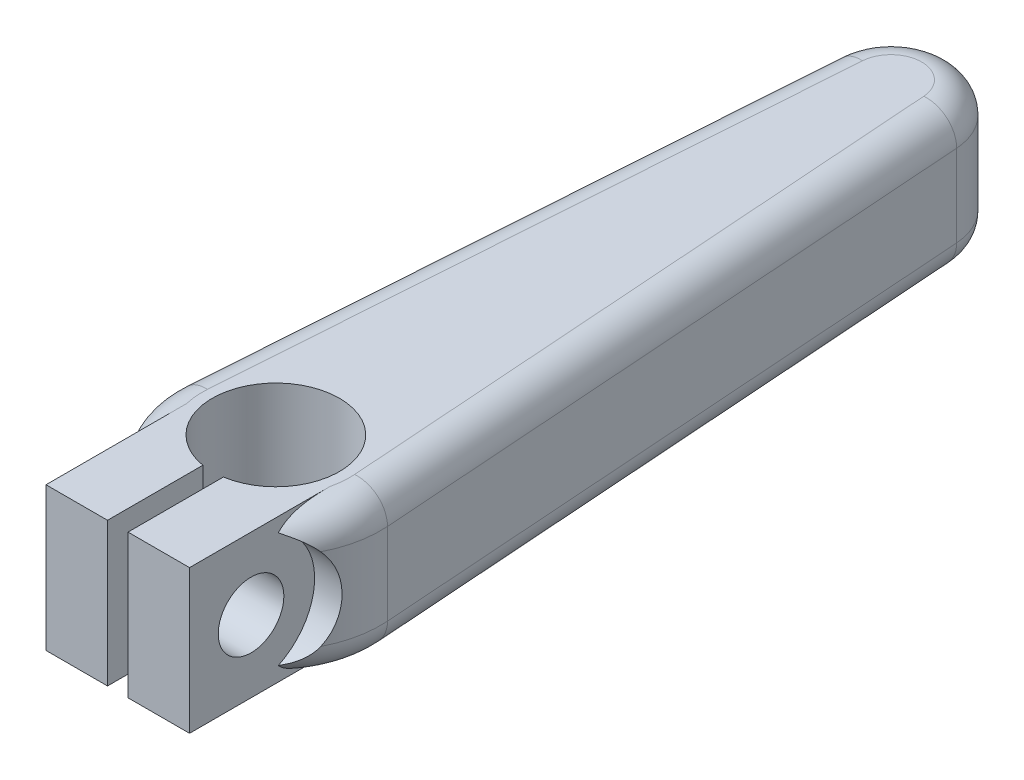
SolidWorks part; units mm, degrees
ref_plane "Front Plane" through (0, 0, 0) normal (0, 0, 1) x (1, 0, 0)
ref_plane "Top Plane" through (0, 0, 0) normal (0, 1, 0) x (1, 0, 0)
ref_plane "Right Plane" through (0, 0, 0) normal (1, 0, 0) x (0, 0, -1)
sketch "Sketch1" plane through (0, 0, 0) normal (0, 1, 0) x (1, 0, 0)
  line L0 (-5.0875, 0.357) -> (-2.9926, 30.21)
  line L1 (5.0875, 0.357) -> (2.9926, 30.21)
  line L2 (-3.5, -3.7094) -> (-3.5, -7.7094)
  line L3 (-3.5, -7.7094) -> (-0.5, -7.7094)
  line L4 (-0.5, -3.0594) -> (-0.5, -7.7094)
  line L5 (0.5, -3.0594) -> (0.5, -7.7094)
  line L6 (0.5, -7.7094) -> (3.5, -7.7094)
  line L7 (3.5, -7.7094) -> (3.5, -3.7094)
  line L8 (0, 0) -> (0, 50000) construction
  line L9 (0.5, -7.7094) -> (-0.5, -7.7094) construction
  circle A3 centre (0, 0) radius 3.1 construction
  arc A4 (2.9926, 30.21) -> (-2.9926, 30.21) centre (0, 30) ccw
  arc A5 (-5.0875, 0.357) -> (5.0875, 0.357) centre (0, 0) ccw construction
  arc A6 (-0.5, -3.0594) -> (0.5, -3.0594) centre (0, 0) cw
  arc A7 (-3.5, -3.7094) -> (-5.0875, 0.357) centre (0, 0) cw
  arc A8 (3.5, -3.7094) -> (5.0875, 0.357) centre (0, 0) ccw
  point P21 (0, -7.7094)
  dimension "D1" = 5.1
  dimension "D2" = 6.2
  dimension "D3" = 3
  dimension "D4" = 30
  dimension "D5" = 0.5
  dimension "D6" = 3
  dimension "D7" = 4
extrude "Boss-Extrude1" add sketch "Sketch1" along normal blind 7 contours L7 A8 L1 A4 L0 A7 L2 L3 L4 A6 L5 L6 region at (0, 0, -12.5772)
sketch "Sketch2" plane through (3.5, 0, 0) normal (1, 0, 0) x (0, 0, -1)
  line L0 (-7.7094, 7) -> (-7.7094, 0) construction
  circle A0 centre (-4.7094, 3.5) radius 1.6
  point P2 (-7.7094, 3.5)
  point P3 (0, 0)
  point P6 (-4.789, 3)
  dimension "D1" = 3.2
  dimension "D2" = 3
extrude "Cut-Extrude1" cut sketch "Sketch2" against normal through all
sketch "Sketch3" plane through (3.5, 0, 0) normal (1, 0, 0) x (0, 0, -1)
  circle A0 centre (-4.7094, 3.5) radius 3.1
  dimension "D1" = 6.2
extrude "Cut-Extrude2" cut sketch "Sketch3" along normal through all
sketch "Sketch4" plane through (-3.5, 0, 0) normal (-1, 0, 0) x (0, 0, 1)
  circle A0 centre (4.7094, 3.5) radius 3.1
  dimension "D1" = 6.2
extrude "Cut-Extrude3" cut sketch "Sketch4" along normal through all
fillet "Fillet1" radius 1.5 10 edges at (-4.7508, 0, 1.8547) (4.7508, 0, 1.8547) (4.0401, 0, -15.2835) (0, 0, -33) (-4.7508, 7, 1.8547) (4.7508, 7, 1.8547) (0, 7, -33) (-4.0401, 0, -15.2835) (4.0401, 7, -15.2835) (-4.0401, 7, -15.2835)
